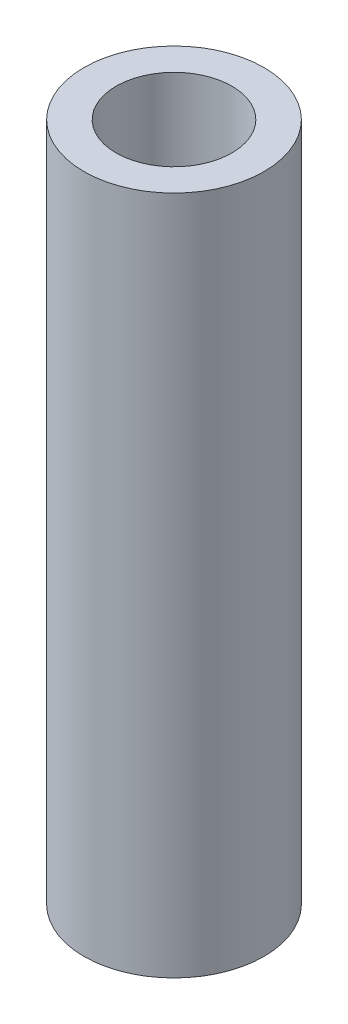
SolidWorks part; units mm, degrees
ref_plane "Front Plane" through (0, 0, 0) normal (0, 0, 1) x (1, 0, 0)
ref_plane "Top Plane" through (0, 0, 0) normal (0, 1, 0) x (1, 0, 0)
ref_plane "Right Plane" through (0, 0, 0) normal (1, 0, 0) x (0, 0, -1)
sketch "Sketch1" plane through (0, 0, 0) normal (0, 1, 0) x (1, 0, 0)
  circle A0 centre (0, 0) radius 3.873
  circle A1 centre (0, 0) radius 2.4892
  dimension "D1" = 7.746
  dimension "D2" = 4.9784
extrude "Boss-Extrude1" add sketch "Sketch1" along normal blind 29.225
